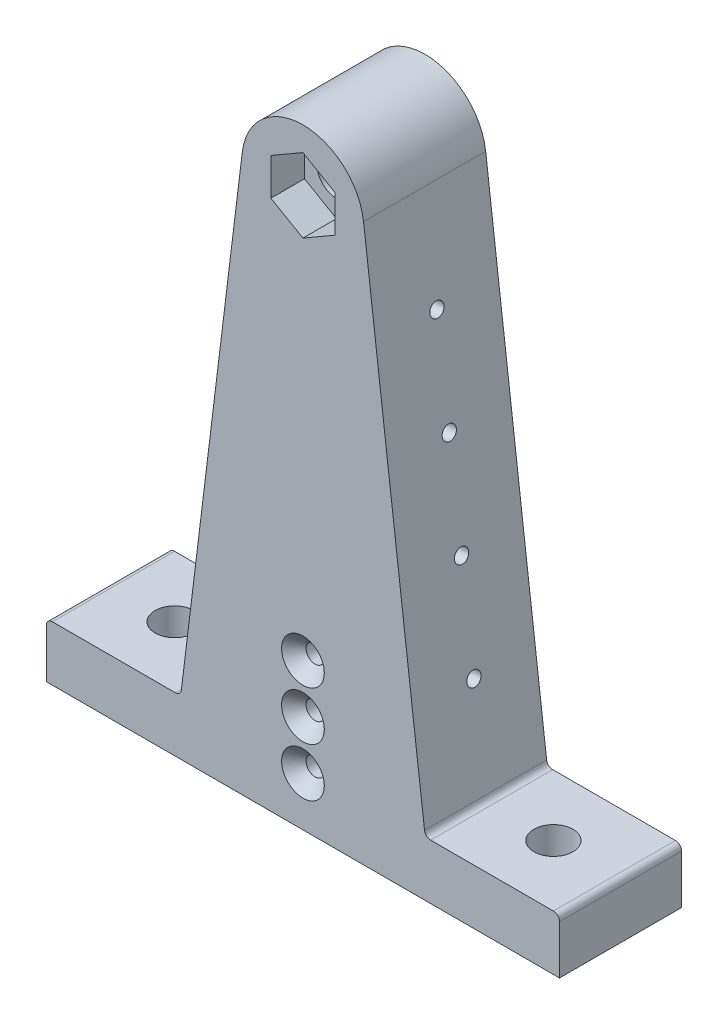
SolidWorks part; units mm, degrees
ref_plane "Front Plane" through (0, 0, 0) normal (0, 0, 1) x (1, 0, 0)
ref_plane "Top Plane" through (0, 0, 0) normal (0, 1, 0) x (1, 0, 0)
ref_plane "Right Plane" through (0, 0, 0) normal (1, 0, 0) x (0, 0, -1)
sketch "Sketch1" plane through (0, 0, 0) normal (0, 0, 1) x (1, 0, 0)
  line L0 (-9.9255, 1.2187) -> (-20.0206, -81)
  line L1 (-20.0206, -81) -> (-42.0206, -81)
  line L2 (-42.0206, -81) -> (-42.0206, -90)
  line L3 (-42.0206, -90) -> (42.0206, -90)
  line L4 (0, 0) -> (0, -90) construction
  line L5 (42.0206, -81) -> (42.0206, -90)
  line L6 (20.0206, -81) -> (42.0206, -81)
  line L7 (9.9255, 1.2187) -> (20.0206, -81)
  circle A0 centre (0, 0) radius 3.2
  circle A1 centre (0, 0) radius 10
  dimension "D1" = 6.4
  dimension "D2" = 20
  dimension "D3" = 90
  dimension "D4" = 9
  dimension "D5" = 22
  dimension "D6" = 7
extrude "Boss-Extrude1" add sketch "Sketch1" along normal blind 20 contours A1 A0 | L0 A1 | A1 | A1 A0 | L0 L1 L2 L3 | L4 L3 L5 L6 L7 region at (0, -57.1621, 0) region at (0, 9.7172, 0)
sketch "Sketch3" plane through (0, -81, 0) normal (0, 1, 0) x (1, 0, 0)
  line L0 (-42.0206, -10) -> (-31.0206, -10) construction
  line L1 (-42.0206, -20) -> (-42.0206, 0) construction
  line L2 (42.0206, -10) -> (31.0206, -10) construction
  line L3 (42.0206, -20) -> (42.0206, 0) construction
  circle A0 centre (-31.0206, -10) radius 3.2
  circle A1 centre (31.0206, -10) radius 3.2
  circle A2 centre (-31.0206, -10) radius 9.5
  circle A3 centre (31.0206, -10) radius 9.5
  dimension "D1" = 6.4
  dimension "D2" = 19
  dimension "D3" = 11
extrude "Cut-Extrude1" cut sketch "Sketch3" against normal through all contours A0 | A1 region at (-31.0206, -81, 10) region at (31.0206, -81, 10)
sketch "Sketch4" plane through (0, 0, 20) normal (0, 0, 1) x (1, 0, 0)
  line L1 (0, 6.0622) -> (-5.25, 3.0311)
  line L2 (-5.25, 3.0311) -> (-5.25, -3.0311)
  line L3 (-5.25, -3.0311) -> (0, -6.0622)
  line L4 (0, -6.0622) -> (5.25, -3.0311)
  line L5 (5.25, -3.0311) -> (5.25, 3.0311)
  line L6 (5.25, 3.0311) -> (0, 6.0622)
  circle A0 centre (0, 0) radius 5.25 construction
  dimension "D1" = 10.5
extrude "Cut-Extrude2" cut sketch "Sketch4" against normal blind 5.5
sketch "Sketch6" plane through (0, 0, 20) normal (0, 0, 1) x (1, 0, 0)
  line L0 (0, -90) -> (0, -82) construction
  line L1 (-42.0206, -90) -> (42.0206, -90) construction
  line L2 (0, -82) -> (0, -74) construction
  line L3 (0, -74) -> (0, -66) construction
  circle A0 centre (0, -66) radius 1.5
  circle A1 centre (0, -74) radius 1.5
  circle A2 centre (0, -82) radius 1.5
  dimension "D1" = 3
  dimension "D2" = 8
extrude "Cut-Extrude4" cut sketch "Sketch6" against normal through all
chamfer "Chamfer1" distance 2 angle 45 3 edges at (1.5, -82, 20) (1.5, -74, 20) (1.5, -66, 20)
sketch "Sketch8" plane through (-9.9255, 1.2187, 0) normal (-0.9925, 0.1219, 0) x (0, 0, 1)
  line L0 (10, 0) -> (10, -16.5672) construction
  line L3 (20, 0) -> (0, 0) construction
  line L4 (10, -16.5672) -> (10, -33.1345) construction
  line L5 (10, -33.1345) -> (10, -49.7017) construction
  line L6 (10, -49.7017) -> (10, -66.2689) construction
  line L7 (10, -66.2689) -> (10, -82.8361) construction
  line L8 (20, -82.8361) -> (0, -82.8361) construction
  circle A0 centre (10, -16.5672) radius 1.16
  circle A1 centre (10, -33.1345) radius 1.16
  circle A2 centre (10, -49.7017) radius 1.16
  circle A3 centre (10, -66.2689) radius 1.16
  dimension "D1" = 2.32
extrude "Cut-Extrude5" cut sketch "Sketch8" against normal blind 10
mirror "Mirror1" about plane through (0, 0, 0) normal (1, 0, 0) of "Cut-Extrude5"
fillet "Fillet1" radius 1 4 edges at (-42.0206, -81, 10) (-20.0206, -81, 10) (42.0206, -81, 10) (20.0206, -81, 10)
